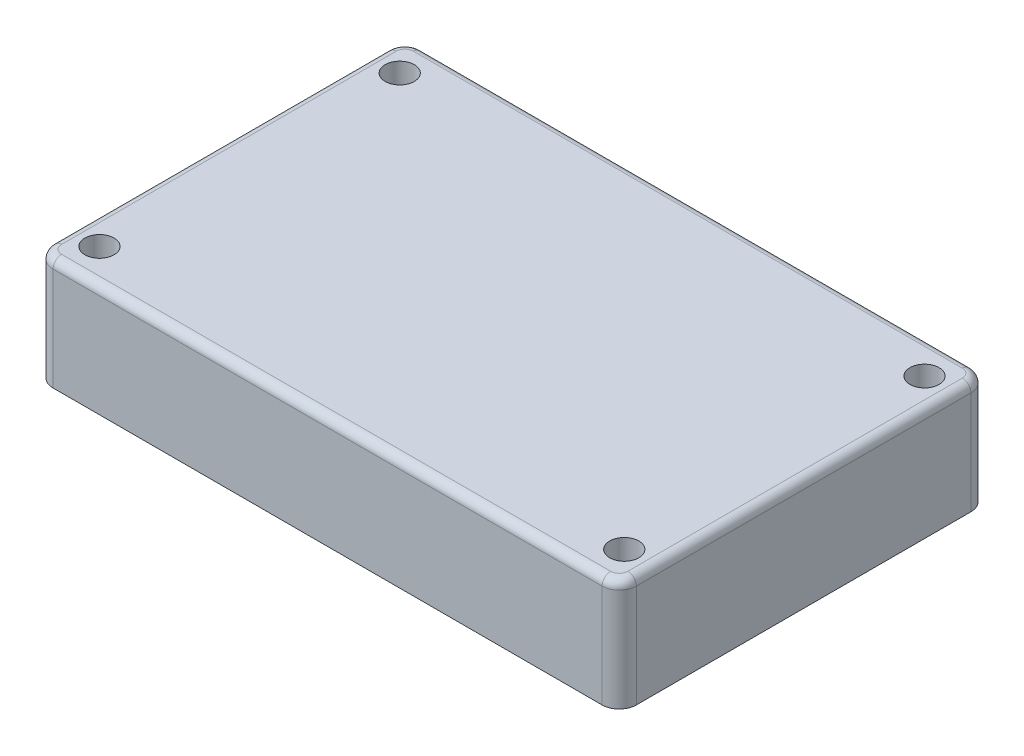
SolidWorks part; units mm, degrees
material "ABS"
ref_plane "Front Plane" through (0, 0, 0) normal (0, 0, 1) x (1, 0, 0)
ref_plane "Top Plane" through (0, 0, 0) normal (0, 1, 0) x (1, 0, 0)
ref_plane "Right Plane" through (0, 0, 0) normal (1, 0, 0) x (0, 0, -1)
ref_plane "Gasket_offset" through (0, 1.6, 0) normal (0, 1, 0) x (1, 0, 0)
sketch "Sketch1" plane through (0, 0, 0) normal (0, 1, 0) x (1, 0, 0)
  line L17 (34, -21.5) -> (-34, -21.5)
  line L18 (34, -21.5) -> (34, 21.5)
  line L19 (34, 21.5) -> (-34, 21.5)
  line L20 (-34, -21.5) -> (-34, 21.5)
  line L21 (34, -21.5) -> (-34, 21.5) construction
  line L22 (34, 21.5) -> (-34, -21.5) construction
  point P3 (0, 0)
  dimension "D1" = 68
  dimension "D2" = 43
extrude "Boss-Extrude1" add sketch "Sketch1" along normal blind 13 from surface starting at plane "Gasket_offset"
shell "Shell1" thickness 4 removed face at (0, 1.6, 0)
fillet "Fillet1" [suppressed] radius 7
sketch "Sketch2" plane through (0, 12.2, 0) normal (0, -1, 0) x (1, 0, 0)
  line L4 (30, 17.5) -> (-30, 17.5)
  line L5 (-30, 17.5) -> (-30, -17.5)
  line L6 (-30, -17.5) -> (30, -17.5)
  line L7 (30, -17.5) -> (30, 17.5)
  line L8 (30, 17.5) -> (-30, 17.5)
  line L9 (-30, 17.5) -> (-30, -17.5)
  line L10 (-30, -17.5) -> (30, -17.5)
  line L11 (30, -17.5) -> (30, 17.5)
  dimension "D1" = 0
chamfer "Chamfer2" distance 2 angle 75 4 edges at (-30, 6.9, 17.5) (-30, 6.9, -17.5) (30, 6.9, -17.5) (30, 6.9, 17.5) first distance on face at (0, 6.9, 17.5) first distance on face at (0, 6.9, -17.5)
sketch "Sketch5" plane through (0, 1.6, 0) normal (0, -1, 0) x (1, 0, 0)
  line L0 (31, 2) -> (31, -2) construction
  line L1 (34, 2) -> (34, -2)
  line L2 (28, 2) -> (28, -2)
  circle A0 centre (31, 0) radius 1 construction
  circle A1 centre (31, 0) radius 3 construction
  arc A2 (34, 2) -> (28, 2) centre (31, 2) ccw
  arc A3 (28, -2) -> (34, -2) centre (31, -2) ccw
  point P4 (31, 0)
  dimension "D1" = 2
  dimension "D2" = 6
  dimension "D3" = 31
  dimension "D4" = 4
extrude "Boss-Extrude2" add sketch "Sketch5" against normal up to surface (10.6 mm away) up to face at (0, 12.2, 0)
fillet "Fillet3" radius 2 10 edges at (-28, 6.9, 17.5) (-30, 6.9, 10.0359) (-30, 6.9, -10.0359) (-28, 6.9, -17.5) (30, 6.9, 10.0359) (28, 6.9, 17.5) (28, 6.9, -17.5) (30, 6.9, -10.0359) (30, 6.9, -4.8284) (30, 6.9, 4.8284)
fillet "Fillet4" radius 2 4 edges at (-34, 8.1, -21.5) (-34, 8.1, 21.5) (34, 8.1, -21.5) (34, 8.1, 21.5)
sketch "Sketch6" plane through (0, 1.6, 0) normal (0, -1, 0) x (1, 0, 0)
  line L0 (31, -2) -> (31, 2) construction
  line L1 (30, -2) -> (30, 2)
  line L2 (32, -2) -> (32, 2)
  circle A0 centre (31, 0) radius 1 construction
  arc A1 (30, -2) -> (32, -2) centre (31, -2) ccw
  arc A2 (32, 2) -> (30, 2) centre (31, 2) ccw
  point P4 (31, 0)
  dimension "D2" = 2
  dimension "D1" = 31
  dimension "D3" = 4
sketch "Sketch9" plane through (0, 0, 0) normal (0, 0, 1) x (1, 0, 0)
  line L0 (31, 1.6) -> (27, 8.5282)
  line L1 (55, 0) -> (-55, 0) construction
  dimension "D1" = 60
  dimension "D2" = 8
hole_wizard "M3 Clearance Hole1" positions "Sketch7" profile "Sketch8" hole size "M3" standard "ISO" end condition through all
sketch "Sketch7" plane through (0, 14.6, 0) normal (0, 1, 0) x (1, 0, 0)
  point P12 (30.5885, 17.5)
  point P15 (-30.5885, 17.5)
  point P18 (30.5885, -17.5)
  point P21 (-30.5885, -17.5)
sketch "Sketch8" plane through (30.5885, 14.6, -17.5) normal (1, 0, 0) x (0, 0, 1)
  line L0 (0, 0) -> (0, 13)
  line L1 (0, 13) -> (1.7, 13)
  line L2 (1.7, 13) -> (1.7, 0)
  line L5 (1.7, 0) -> (0, 0)
  line L11 (0, -6.35) -> (0, 107.95) construction
  dimension "Thru Hole Dia." = 3.4
  dimension "Thru Hole Depth" = 13
sweep "Cut-Sweep1" cut profiles "Sketch6" path "Sketch9"
fillet "Fillet5" radius 1 8 edges at (33.4142, 14.6, 20.9142) (34, 14.6, 0) (33.4142, 14.6, -20.9142) (0, 14.6, -21.5) (-33.4142, 14.6, -20.9142) (-34, 14.6, 0) (-33.4142, 14.6, 20.9142) (0, 14.6, 21.5)
